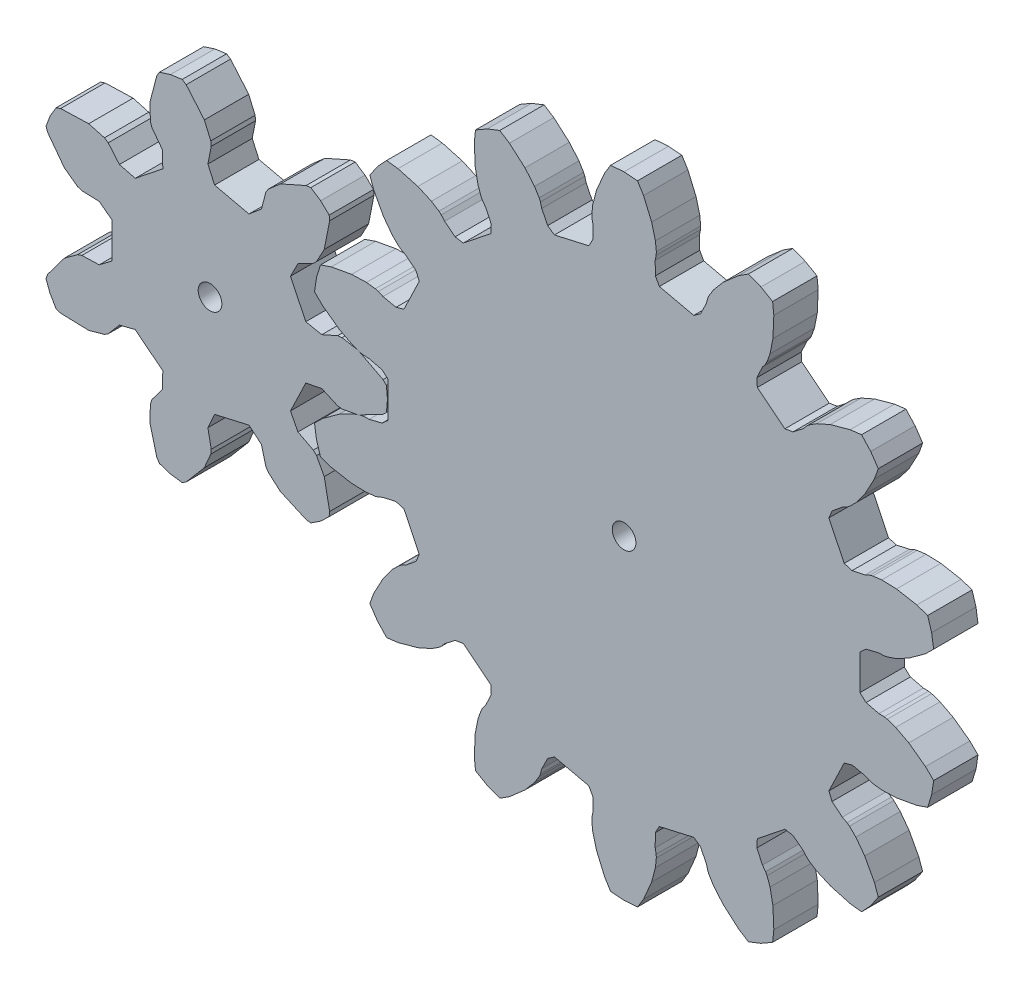
SolidWorks part; units mm, degrees
material "Corrugated Paper"
ref_plane "Front Plane" through (0, 0, 0) normal (0, 0, 1) x (1, 0, 0)
ref_plane "Top Plane" through (0, 0, 0) normal (0, 1, 0) x (1, 0, 0)
ref_plane "Right Plane" through (0, 0, 0) normal (1, 0, 0) x (0, 0, -1)
sketch "Model" plane through (0, 0, 0) normal (0, 0, 1) x (1, 0, 0)
  line L0 (10.824, -15.5893) -> (11.8775, -14.8939)
  line L1 (11.8775, -14.8939) -> (12.7899, -14.0216)
  line L2 (12.7899, -14.0216) -> (12.8434, -13.5144)
  line L3 (12.8434, -13.5144) -> (12.2623, -10.5576)
  line L4 (12.2623, -10.5576) -> (11.4342, -9.0171)
  line L5 (11.4342, -9.0171) -> (11.0892, -8.677)
  line L6 (11.0892, -8.677) -> (9.4401, -7.8202)
  line L7 (9.4401, -7.8202) -> (8.6391, -6.2612)
  line L8 (8.6391, -6.2612) -> (10.2816, -2.8505)
  line L9 (10.2816, -2.8505) -> (11.9999, -2.5047)
  line L10 (11.9999, -2.5047) -> (13.698, -3.2599)
  line L11 (13.698, -3.2599) -> (14.179, -3.3175)
  line L12 (14.179, -3.3175) -> (15.8632, -3.0111)
  line L13 (15.8632, -3.0111) -> (15.2951, -3.2054)
  line L14 (15.2951, -3.2054) -> (13.8858, -3.9376)
  line L15 (13.8858, -3.9376) -> (12.0928, -5.2415)
  line L16 (12.0928, -5.2415) -> (11.2168, -6.1052)
  line L17 (11.2168, -6.1052) -> (11.4324, -7.536)
  line L18 (11.4324, -7.536) -> (11.8589, -8.9187)
  line L19 (11.8589, -8.9187) -> (13.023, -9.3169)
  line L20 (13.023, -9.3169) -> (15.2041, -9.7136)
  line L21 (15.2041, -9.7136) -> (16.7916, -9.7618)
  line L22 (16.7916, -9.7618) -> (17.7443, -9.6477)
  line L23 (17.7443, -9.6477) -> (18.0633, -9.5598)
  line L24 (18.0633, -9.5598) -> (18.5734, -9.3329)
  line L25 (18.5734, -9.3329) -> (19.9687, -9.0348)
  line L26 (19.9687, -9.0348) -> (20.819, -9.2793)
  line L27 (20.819, -9.2793) -> (22.4615, -12.6899)
  line L28 (22.4615, -12.6899) -> (22.1225, -13.5071)
  line L29 (22.1225, -13.5071) -> (21.0194, -14.4122)
  line L30 (21.0194, -14.4122) -> (20.524, -14.6696)
  line L31 (20.524, -14.6696) -> (20.2564, -14.8641)
  line L32 (20.2564, -14.8641) -> (19.5731, -15.5378)
  line L33 (19.5731, -15.5378) -> (18.621, -16.809)
  line L34 (18.621, -16.809) -> (17.5714, -18.7617)
  line L35 (17.5714, -18.7617) -> (17.1569, -19.92)
  line L36 (17.1569, -19.92) -> (17.972, -21.1155)
  line L37 (17.972, -21.1155) -> (18.9562, -22.1762)
  line L38 (18.9562, -22.1762) -> (20.1777, -22.0299)
  line L39 (20.1777, -22.0299) -> (22.3149, -21.441)
  line L40 (22.3149, -21.441) -> (23.7661, -20.7956)
  line L41 (23.7661, -20.7956) -> (24.575, -20.2794)
  line L42 (24.575, -20.2794) -> (24.8242, -20.0619)
  line L43 (24.8242, -20.0619) -> (25.1854, -19.6361)
  line L44 (25.1854, -19.6361) -> (26.3132, -18.7621)
  line L45 (26.3132, -18.7621) -> (27.1854, -18.6134)
  line L46 (27.1854, -18.6134) -> (30.145, -20.9737)
  line L47 (30.145, -20.9737) -> (30.1941, -21.8571)
  line L48 (30.1941, -21.8571) -> (29.593, -23.151)
  line L49 (29.593, -23.151) -> (29.2583, -23.5979)
  line L50 (29.2583, -23.5979) -> (29.1016, -23.8893)
  line L51 (29.1016, -23.8893) -> (28.7783, -24.7928)
  line L52 (28.7783, -24.7928) -> (28.4721, -26.3512)
  line L53 (28.4721, -26.3512) -> (28.3736, -28.5659)
  line L54 (28.3736, -28.5659) -> (28.5027, -29.7893)
  line L55 (28.5027, -29.7893) -> (29.7558, -30.5128)
  line L56 (29.7558, -30.5128) -> (31.1028, -31.0414)
  line L57 (31.1028, -31.0414) -> (32.1398, -30.3796)
  line L58 (32.1398, -30.3796) -> (33.8099, -28.9217)
  line L59 (33.8099, -28.9217) -> (34.8374, -27.7106)
  line L60 (34.8374, -27.7106) -> (35.3421, -26.8946)
  line L61 (35.3421, -26.8946) -> (35.4723, -26.5904)
  line L62 (35.4723, -26.5904) -> (35.613, -26.0501)
  line L63 (35.613, -26.0501) -> (36.2499, -24.7734)
  line L64 (36.2499, -24.7734) -> (36.9712, -24.261)
  line L65 (36.9712, -24.261) -> (40.6618, -25.1033)
  line L66 (40.6618, -25.1033) -> (41.0893, -25.8779)
  line L67 (41.0893, -25.8779) -> (41.1092, -27.3046)
  line L68 (41.1092, -27.3046) -> (41.0015, -27.8524)
  line L69 (41.0015, -27.8524) -> (40.9868, -28.183)
  line L70 (40.9868, -28.183) -> (41.0875, -29.1372)
  line L71 (41.0875, -29.1372) -> (41.4877, -30.6741)
  line L72 (41.4877, -30.6741) -> (42.3599, -32.7123)
  line L73 (42.3599, -32.7123) -> (43.0071, -33.7585)
  line L74 (43.0071, -33.7585) -> (44.45, -33.8667)
  line L75 (44.45, -33.8667) -> (45.8929, -33.7585)
  line L76 (45.8929, -33.7585) -> (46.5401, -32.7123)
  line L77 (46.5401, -32.7123) -> (47.4123, -30.6741)
  line L78 (47.4123, -30.6741) -> (47.8125, -29.1372)
  line L79 (47.8125, -29.1372) -> (47.9132, -28.183)
  line L80 (47.9132, -28.183) -> (47.8985, -27.8524)
  line L81 (47.8985, -27.8524) -> (47.7908, -27.3046)
  line L82 (47.7908, -27.3046) -> (47.8107, -25.8779)
  line L83 (47.8107, -25.8779) -> (48.2382, -25.1033)
  line L84 (48.2382, -25.1033) -> (51.9288, -24.261)
  line L85 (51.9288, -24.261) -> (52.6501, -24.7734)
  line L86 (52.6501, -24.7734) -> (53.287, -26.0501)
  line L87 (53.287, -26.0501) -> (53.4277, -26.5904)
  line L88 (53.4277, -26.5904) -> (53.5579, -26.8946)
  line L89 (53.5579, -26.8946) -> (54.0626, -27.7106)
  line L90 (54.0626, -27.7106) -> (55.0901, -28.9217)
  line L91 (55.0901, -28.9217) -> (56.7602, -30.3796)
  line L92 (56.7602, -30.3796) -> (57.7972, -31.0414)
  line L93 (57.7972, -31.0414) -> (59.1442, -30.5128)
  line L94 (59.1442, -30.5128) -> (60.3973, -29.7893)
  line L95 (60.3973, -29.7893) -> (60.5264, -28.5659)
  line L96 (60.5264, -28.5659) -> (60.4279, -26.3512)
  line L97 (60.4279, -26.3512) -> (60.1217, -24.7928)
  line L98 (60.1217, -24.7928) -> (59.7984, -23.8893)
  line L99 (59.7984, -23.8893) -> (59.6417, -23.5979)
  line L100 (59.6417, -23.5979) -> (59.307, -23.151)
  line L101 (59.307, -23.151) -> (58.7059, -21.8571)
  line L102 (58.7059, -21.8571) -> (58.755, -20.9737)
  line L103 (58.755, -20.9737) -> (61.7146, -18.6134)
  line L104 (61.7146, -18.6134) -> (62.5868, -18.7621)
  line L105 (62.5868, -18.7621) -> (63.7146, -19.6361)
  line L106 (63.7146, -19.6361) -> (64.0758, -20.0619)
  line L107 (64.0758, -20.0619) -> (64.325, -20.2794)
  line L108 (64.325, -20.2794) -> (65.1339, -20.7956)
  line L109 (65.1339, -20.7956) -> (66.5851, -21.441)
  line L110 (66.5851, -21.441) -> (68.7223, -22.0299)
  line L111 (68.7223, -22.0299) -> (69.9438, -22.1762)
  line L112 (69.9438, -22.1762) -> (70.928, -21.1155)
  line L113 (70.928, -21.1155) -> (71.7431, -19.92)
  line L114 (71.7431, -19.92) -> (71.3286, -18.7617)
  line L115 (71.3286, -18.7617) -> (70.279, -16.809)
  line L116 (70.279, -16.809) -> (69.3269, -15.5378)
  line L117 (69.3269, -15.5378) -> (68.6436, -14.8641)
  line L118 (68.6436, -14.8641) -> (68.376, -14.6696)
  line L119 (68.376, -14.6696) -> (67.8806, -14.4122)
  line L120 (67.8806, -14.4122) -> (66.7775, -13.5071)
  line L121 (66.7775, -13.5071) -> (66.4385, -12.6899)
  line L122 (66.4385, -12.6899) -> (68.081, -9.2793)
  line L123 (68.081, -9.2793) -> (68.9313, -9.0348)
  line L124 (68.9313, -9.0348) -> (70.3266, -9.3329)
  line L125 (70.3266, -9.3329) -> (70.8367, -9.5598)
  line L126 (70.8367, -9.5598) -> (71.1557, -9.6477)
  line L127 (71.1557, -9.6477) -> (72.1084, -9.7618)
  line L128 (72.1084, -9.7618) -> (73.6959, -9.7136)
  line L129 (73.6959, -9.7136) -> (75.877, -9.3169)
  line L130 (75.877, -9.3169) -> (77.0411, -8.9187)
  line L131 (77.0411, -8.9187) -> (77.4676, -7.536)
  line L132 (77.4676, -7.536) -> (77.6832, -6.1052)
  line L133 (77.6832, -6.1052) -> (76.8072, -5.2415)
  line L134 (76.8072, -5.2415) -> (75.0142, -3.9376)
  line L135 (75.0142, -3.9376) -> (73.6049, -3.2054)
  line L136 (73.6049, -3.2054) -> (72.697, -2.8949)
  line L137 (72.697, -2.8949) -> (72.3715, -2.8357)
  line L138 (72.3715, -2.8357) -> (71.8134, -2.8188)
  line L139 (71.8134, -2.8188) -> (70.4269, -2.482)
  line L140 (70.4269, -2.482) -> (69.7669, -1.8928)
  line L141 (69.7669, -1.8928) -> (69.7669, 1.8928)
  line L142 (69.7669, 1.8928) -> (70.4269, 2.482)
  line L143 (70.4269, 2.482) -> (71.8134, 2.8188)
  line L144 (71.8134, 2.8188) -> (72.3715, 2.8357)
  line L145 (72.3715, 2.8357) -> (72.697, 2.8949)
  line L146 (72.697, 2.8949) -> (73.6049, 3.2054)
  line L147 (73.6049, 3.2054) -> (75.0142, 3.9376)
  line L148 (75.0142, 3.9376) -> (76.8072, 5.2415)
  line L149 (76.8072, 5.2415) -> (77.6832, 6.1052)
  line L150 (77.6832, 6.1052) -> (77.4676, 7.536)
  line L151 (77.4676, 7.536) -> (77.0411, 8.9187)
  line L152 (77.0411, 8.9187) -> (75.877, 9.3169)
  line L153 (75.877, 9.3169) -> (73.6959, 9.7136)
  line L154 (73.6959, 9.7136) -> (72.1084, 9.7618)
  line L155 (72.1084, 9.7618) -> (71.1557, 9.6477)
  line L156 (71.1557, 9.6477) -> (70.8367, 9.5598)
  line L157 (70.8367, 9.5598) -> (70.3266, 9.3329)
  line L158 (70.3266, 9.3329) -> (68.9313, 9.0348)
  line L159 (68.9313, 9.0348) -> (68.081, 9.2793)
  line L160 (68.081, 9.2793) -> (66.4385, 12.6899)
  line L161 (66.4385, 12.6899) -> (66.7775, 13.5071)
  line L162 (66.7775, 13.5071) -> (67.8806, 14.4122)
  line L163 (67.8806, 14.4122) -> (68.376, 14.6696)
  line L164 (68.376, 14.6696) -> (68.6436, 14.8641)
  line L165 (68.6436, 14.8641) -> (69.3269, 15.5378)
  line L166 (69.3269, 15.5378) -> (70.279, 16.809)
  line L167 (70.279, 16.809) -> (71.3286, 18.7617)
  line L168 (71.3286, 18.7617) -> (71.7431, 19.92)
  line L169 (71.7431, 19.92) -> (70.928, 21.1155)
  line L170 (70.928, 21.1155) -> (69.9438, 22.1762)
  line L171 (69.9438, 22.1762) -> (68.7223, 22.0299)
  line L172 (68.7223, 22.0299) -> (66.5851, 21.441)
  line L173 (66.5851, 21.441) -> (65.1339, 20.7956)
  line L174 (65.1339, 20.7956) -> (64.325, 20.2794)
  line L175 (64.325, 20.2794) -> (64.0758, 20.0619)
  line L176 (64.0758, 20.0619) -> (63.7146, 19.6361)
  line L177 (63.7146, 19.6361) -> (62.5868, 18.7621)
  line L178 (62.5868, 18.7621) -> (61.7146, 18.6134)
  line L179 (61.7146, 18.6134) -> (58.755, 20.9737)
  line L180 (58.755, 20.9737) -> (58.7059, 21.8571)
  line L181 (58.7059, 21.8571) -> (59.307, 23.151)
  line L182 (59.307, 23.151) -> (59.6417, 23.5979)
  line L183 (59.6417, 23.5979) -> (59.7984, 23.8893)
  line L184 (59.7984, 23.8893) -> (60.1217, 24.7928)
  line L185 (60.1217, 24.7928) -> (60.4279, 26.3512)
  line L186 (60.4279, 26.3512) -> (60.5264, 28.5659)
  line L187 (60.5264, 28.5659) -> (60.3973, 29.7893)
  line L188 (60.3973, 29.7893) -> (59.1442, 30.5128)
  line L189 (59.1442, 30.5128) -> (57.7972, 31.0414)
  line L190 (57.7972, 31.0414) -> (56.7602, 30.3796)
  line L191 (56.7602, 30.3796) -> (55.0901, 28.9217)
  line L192 (55.0901, 28.9217) -> (54.0626, 27.7106)
  line L193 (54.0626, 27.7106) -> (53.5579, 26.8946)
  line L194 (53.5579, 26.8946) -> (53.4277, 26.5904)
  line L195 (53.4277, 26.5904) -> (53.287, 26.0501)
  line L196 (53.287, 26.0501) -> (52.6501, 24.7734)
  line L197 (52.6501, 24.7734) -> (51.9288, 24.261)
  line L198 (51.9288, 24.261) -> (48.2382, 25.1033)
  line L199 (48.2382, 25.1033) -> (47.8107, 25.8779)
  line L200 (47.8107, 25.8779) -> (47.7908, 27.3046)
  line L201 (47.7908, 27.3046) -> (47.8985, 27.8524)
  line L202 (47.8985, 27.8524) -> (47.9132, 28.183)
  line L203 (47.9132, 28.183) -> (47.8125, 29.1372)
  line L204 (47.8125, 29.1372) -> (47.4123, 30.6741)
  line L205 (47.4123, 30.6741) -> (46.5401, 32.7123)
  line L206 (46.5401, 32.7123) -> (45.8929, 33.7585)
  line L207 (45.8929, 33.7585) -> (44.45, 33.8667)
  line L208 (44.45, 33.8667) -> (43.0071, 33.7585)
  line L209 (43.0071, 33.7585) -> (42.3599, 32.7123)
  line L210 (42.3599, 32.7123) -> (41.4877, 30.6741)
  line L211 (41.4877, 30.6741) -> (41.0875, 29.1372)
  line L212 (41.0875, 29.1372) -> (40.9868, 28.183)
  line L213 (40.9868, 28.183) -> (41.0015, 27.8524)
  line L214 (41.0015, 27.8524) -> (41.1092, 27.3046)
  line L215 (41.1092, 27.3046) -> (41.0893, 25.8779)
  line L216 (41.0893, 25.8779) -> (40.6618, 25.1033)
  line L217 (40.6618, 25.1033) -> (36.9712, 24.261)
  line L218 (36.9712, 24.261) -> (36.2499, 24.7734)
  line L219 (36.2499, 24.7734) -> (35.613, 26.0501)
  line L220 (35.613, 26.0501) -> (35.4723, 26.5904)
  line L221 (35.4723, 26.5904) -> (35.3421, 26.8946)
  line L222 (35.3421, 26.8946) -> (34.8374, 27.7106)
  line L223 (34.8374, 27.7106) -> (33.8099, 28.9217)
  line L224 (33.8099, 28.9217) -> (32.1398, 30.3796)
  line L225 (32.1398, 30.3796) -> (31.1028, 31.0414)
  line L226 (31.1028, 31.0414) -> (29.7558, 30.5128)
  line L227 (29.7558, 30.5128) -> (28.5027, 29.7893)
  line L228 (28.5027, 29.7893) -> (28.3736, 28.5659)
  line L229 (28.3736, 28.5659) -> (28.4721, 26.3512)
  line L230 (28.4721, 26.3512) -> (28.7783, 24.7928)
  line L231 (28.7783, 24.7928) -> (29.1016, 23.8893)
  line L232 (29.1016, 23.8893) -> (29.2583, 23.5979)
  line L233 (29.2583, 23.5979) -> (29.593, 23.151)
  line L234 (29.593, 23.151) -> (30.1941, 21.8571)
  line L235 (30.1941, 21.8571) -> (30.145, 20.9737)
  line L236 (30.145, 20.9737) -> (27.1854, 18.6134)
  line L237 (27.1854, 18.6134) -> (26.3132, 18.7621)
  line L238 (26.3132, 18.7621) -> (25.1854, 19.6361)
  line L239 (25.1854, 19.6361) -> (24.8242, 20.0619)
  line L240 (24.8242, 20.0619) -> (24.575, 20.2794)
  line L241 (24.575, 20.2794) -> (23.7661, 20.7956)
  line L242 (23.7661, 20.7956) -> (22.3149, 21.441)
  line L243 (22.3149, 21.441) -> (20.1777, 22.0299)
  line L244 (20.1777, 22.0299) -> (18.9562, 22.1762)
  line L245 (18.9562, 22.1762) -> (17.972, 21.1155)
  line L246 (17.972, 21.1155) -> (17.1569, 19.92)
  line L247 (17.1569, 19.92) -> (17.5714, 18.7617)
  line L248 (17.5714, 18.7617) -> (18.621, 16.809)
  line L249 (18.621, 16.809) -> (19.5731, 15.5378)
  line L250 (19.5731, 15.5378) -> (20.2564, 14.8641)
  line L251 (20.2564, 14.8641) -> (20.524, 14.6696)
  line L252 (20.524, 14.6696) -> (21.0194, 14.4122)
  line L253 (21.0194, 14.4122) -> (22.1225, 13.5071)
  line L254 (22.1225, 13.5071) -> (22.4615, 12.6899)
  line L255 (22.4615, 12.6899) -> (20.819, 9.2793)
  line L256 (20.819, 9.2793) -> (19.9687, 9.0348)
  line L257 (19.9687, 9.0348) -> (18.5734, 9.3329)
  line L258 (18.5734, 9.3329) -> (18.0633, 9.5598)
  line L259 (18.0633, 9.5598) -> (17.7443, 9.6477)
  line L260 (17.7443, 9.6477) -> (16.7916, 9.7618)
  line L261 (16.7916, 9.7618) -> (15.2041, 9.7136)
  line L262 (15.2041, 9.7136) -> (13.023, 9.3169)
  line L263 (13.023, 9.3169) -> (11.8589, 8.9187)
  line L264 (11.8589, 8.9187) -> (11.4324, 7.536)
  line L265 (11.4324, 7.536) -> (11.2168, 6.1052)
  line L266 (11.2168, 6.1052) -> (12.0928, 5.2415)
  line L267 (12.0928, 5.2415) -> (13.8858, 3.9376)
  line L268 (13.8858, 3.9376) -> (15.2951, 3.2054)
  line L269 (15.2951, 3.2054) -> (15.8632, 3.0111)
  line L270 (15.8632, 3.0111) -> (14.179, 3.3175)
  line L271 (14.179, 3.3175) -> (13.698, 3.2599)
  line L272 (13.698, 3.2599) -> (11.9999, 2.5047)
  line L273 (11.9999, 2.5047) -> (10.2816, 2.8505)
  line L274 (10.2816, 2.8505) -> (8.6391, 6.2612)
  line L275 (8.6391, 6.2612) -> (9.4401, 7.8202)
  line L276 (9.4401, 7.8202) -> (11.0892, 8.677)
  line L277 (11.0892, 8.677) -> (11.4342, 9.0171)
  line L278 (11.4342, 9.0171) -> (12.2623, 10.5576)
  line L279 (12.2623, 10.5576) -> (12.8434, 13.5144)
  line L280 (12.8434, 13.5144) -> (12.7899, 14.0216)
  line L281 (12.7899, 14.0216) -> (11.8775, 14.8939)
  line L282 (11.8775, 14.8939) -> (10.824, 15.5893)
  line L283 (10.824, 15.5893) -> (10.3177, 15.5286)
  line L284 (10.3177, 15.5286) -> (7.5643, 14.3042)
  line L285 (7.5643, 14.3042) -> (6.2467, 13.154)
  line L286 (6.2467, 13.154) -> (5.9919, 12.742)
  line L287 (5.9919, 12.742) -> (5.5235, 10.9436)
  line L288 (5.5235, 10.9436) -> (4.1818, 9.8158)
  line L289 (4.1818, 9.8158) -> (0.4912, 10.6581)
  line L290 (0.4912, 10.6581) -> (-0.2283, 12.2564)
  line L291 (-0.2283, 12.2564) -> (0.1301, 14.0799)
  line L292 (0.1301, 14.0799) -> (0.0792, 14.5617)
  line L293 (0.0792, 14.5617) -> (-0.6088, 16.1696)
  line L294 (-0.6088, 16.1696) -> (-2.5583, 18.4675)
  line L295 (-2.5583, 18.4675) -> (-2.9881, 18.7418)
  line L296 (-2.9881, 18.7418) -> (-4.239, 18.5724)
  line L297 (-4.239, 18.5724) -> (-5.4396, 18.1823)
  line L298 (-5.4396, 18.1823) -> (-5.7078, 17.7486)
  line L299 (-5.7078, 17.7486) -> (-6.4672, 14.8325)
  line L300 (-6.4672, 14.8325) -> (-6.3895, 13.0853)
  line L301 (-6.3895, 13.0853) -> (-6.2262, 12.6291)
  line L302 (-6.2262, 12.6291) -> (-5.1122, 11.1417)
  line L303 (-5.1122, 11.1417) -> (-5.067, 9.3895)
  line L304 (-5.067, 9.3895) -> (-8.0266, 7.0293)
  line L305 (-8.0266, 7.0293) -> (-9.7248, 7.4633)
  line L306 (-9.7248, 7.4633) -> (-10.927, 8.8804)
  line L307 (-10.927, 8.8804) -> (-11.3354, 9.141)
  line L308 (-11.3354, 9.141) -> (-13.0215, 9.6056)
  line L309 (-13.0215, 9.6056) -> (-16.0335, 9.5141)
  line L310 (-16.0335, 9.5141) -> (-16.516, 9.3491)
  line L311 (-16.516, 9.3491) -> (-17.1635, 8.2655)
  line L312 (-17.1635, 8.2655) -> (-17.607, 7.0837)
  line L313 (-17.607, 7.0837) -> (-17.4352, 6.6035)
  line L314 (-17.4352, 6.6035) -> (-15.6287, 4.1916)
  line L315 (-15.6287, 4.1916) -> (-14.2142, 3.163)
  line L316 (-14.2142, 3.163) -> (-13.7559, 3.0063)
  line L317 (-13.7559, 3.0063) -> (-11.8983, 2.9499)
  line L318 (-11.8983, 2.9499) -> (-10.5002, 1.8928)
  line L319 (-10.5002, 1.8928) -> (-10.5002, -1.8928)
  line L320 (-10.5002, -1.8928) -> (-11.8983, -2.9499)
  line L321 (-11.8983, -2.9499) -> (-13.7559, -3.0063)
  line L322 (-13.7559, -3.0063) -> (-14.2142, -3.163)
  line L323 (-14.2142, -3.163) -> (-15.6287, -4.1916)
  line L324 (-15.6287, -4.1916) -> (-17.4352, -6.6035)
  line L325 (-17.4352, -6.6035) -> (-17.607, -7.0837)
  line L326 (-17.607, -7.0837) -> (-17.1635, -8.2655)
  line L327 (-17.1635, -8.2655) -> (-16.516, -9.3491)
  line L328 (-16.516, -9.3491) -> (-16.0335, -9.5141)
  line L329 (-16.0335, -9.5141) -> (-13.0215, -9.6056)
  line L330 (-13.0215, -9.6056) -> (-11.3354, -9.141)
  line L331 (-11.3354, -9.141) -> (-10.927, -8.8804)
  line L332 (-10.927, -8.8804) -> (-9.7248, -7.4633)
  line L333 (-9.7248, -7.4633) -> (-8.0266, -7.0293)
  line L334 (-8.0266, -7.0293) -> (-5.067, -9.3895)
  line L335 (-5.067, -9.3895) -> (-5.1122, -11.1417)
  line L336 (-5.1122, -11.1417) -> (-6.2262, -12.6291)
  line L337 (-6.2262, -12.6291) -> (-6.3895, -13.0853)
  line L338 (-6.3895, -13.0853) -> (-6.4672, -14.8325)
  line L339 (-6.4672, -14.8325) -> (-5.7078, -17.7486)
  line L340 (-5.7078, -17.7486) -> (-5.4396, -18.1823)
  line L341 (-5.4396, -18.1823) -> (-4.239, -18.5724)
  line L342 (-4.239, -18.5724) -> (-2.9881, -18.7418)
  line L343 (-2.9881, -18.7418) -> (-2.5583, -18.4675)
  line L344 (-2.5583, -18.4675) -> (-0.6088, -16.1696)
  line L345 (-0.6088, -16.1696) -> (0.0792, -14.5617)
  line L346 (0.0792, -14.5617) -> (0.1301, -14.0799)
  line L347 (0.1301, -14.0799) -> (-0.2283, -12.2564)
  line L348 (-0.2283, -12.2564) -> (0.4912, -10.6581)
  line L349 (0.4912, -10.6581) -> (4.1818, -9.8158)
  line L350 (4.1818, -9.8158) -> (5.5235, -10.9436)
  line L351 (5.5235, -10.9436) -> (5.9919, -12.742)
  line L352 (5.9919, -12.742) -> (6.2467, -13.154)
  line L353 (6.2467, -13.154) -> (7.5643, -14.3042)
  line L354 (7.5643, -14.3042) -> (10.3177, -15.5286)
  line L355 (10.3177, -15.5286) -> (10.824, -15.5893)
  line L356 (15.9326, -2.9874) -> (18.5737, -1.6153)
  line L357 (18.5737, -1.6153) -> (18.9368, -1.2572)
  line L358 (18.9368, -1.2572) -> (19.05, 0)
  line L359 (19.05, 0) -> (18.9368, 1.2572)
  line L360 (18.9368, 1.2572) -> (18.5737, 1.6153)
  line L361 (18.5737, 1.6153) -> (15.9326, 2.9874)
  line L362 (15.9326, 2.9874) -> (16.203, 2.8949)
  line L363 (16.203, 2.8949) -> (16.5285, 2.8357)
  line L364 (16.5285, 2.8357) -> (17.0866, 2.8188)
  line L365 (17.0866, 2.8188) -> (18.4731, 2.482)
  line L366 (18.4731, 2.482) -> (19.1331, 1.8928)
  line L367 (19.1331, 1.8928) -> (19.1331, -1.8928)
  line L368 (19.1331, -1.8928) -> (18.4731, -2.482)
  line L369 (18.4731, -2.482) -> (17.0866, -2.8188)
  line L370 (17.0866, -2.8188) -> (16.5285, -2.8357)
  line L371 (16.5285, -2.8357) -> (16.203, -2.8949)
  line L372 (16.203, -2.8949) -> (15.9326, -2.9874)
  line L435 (15.8632, 3.0111) -> (15.9326, 2.9874)
  line L436 (15.9326, -2.9874) -> (15.8632, -3.0111)
  circle A0 centre (0, 0) radius 1.27
  circle A1 centre (44.45, 0) radius 1.27
  point P433 (44.45, 0)
  dimension "D2" = 2.54
  dimension "D3" = 2.54
  dimension "D1" = 44.45
extrude "Boss-Extrude2" add sketch "Model" along normal blind 4.7625 contours L436 L356 L357 L358 L359 L360 L361 L435 L270 L271 L272 L273 L274 L275 L276 L277 L278 L279 L280 L281 L282 L283 L284 L285 L286 L287 L288 L289 L290 L291 L292 L293 L294 L295 L296 L297 L298 L299 L300 L301 L302 L303 L304 L305 L306 L307 L308 L309 L310 L311 L312 region at (10.6332, -15.0384, 0)
extrude "Boss-Extrude3" add sketch "Model<4>" along normal blind 4.7625 separate body contours L372 L436 L13 L14 L15 L16 L17 L18 L19 L20 L21 L22 L23 L24 L25 L26 L27 L28 L29 L30 L31 L32 L33 L34 L35 L36 L37 L38 L39 L40 L41 L42 L43 L44 L45 L46 L47 L48 L49 L50 L51 L52 L53 L54 L55 L56 L57 L58 L59 L60 L61 region at (16.205, -3.8972, 0)
sketch "Model<4>" plane through (0, 0, 0) normal (0, 0, 1) x (1, 0, 0) same geometry as "Model"
equation "\"rodThick\"= 0.1in"
equation "\"thick\"= 3 / 16"
equation "\"D1@Boss-Extrude2\"=\"thick\""
equation "\"D1@Boss-Extrude3\"=\"thick\""
